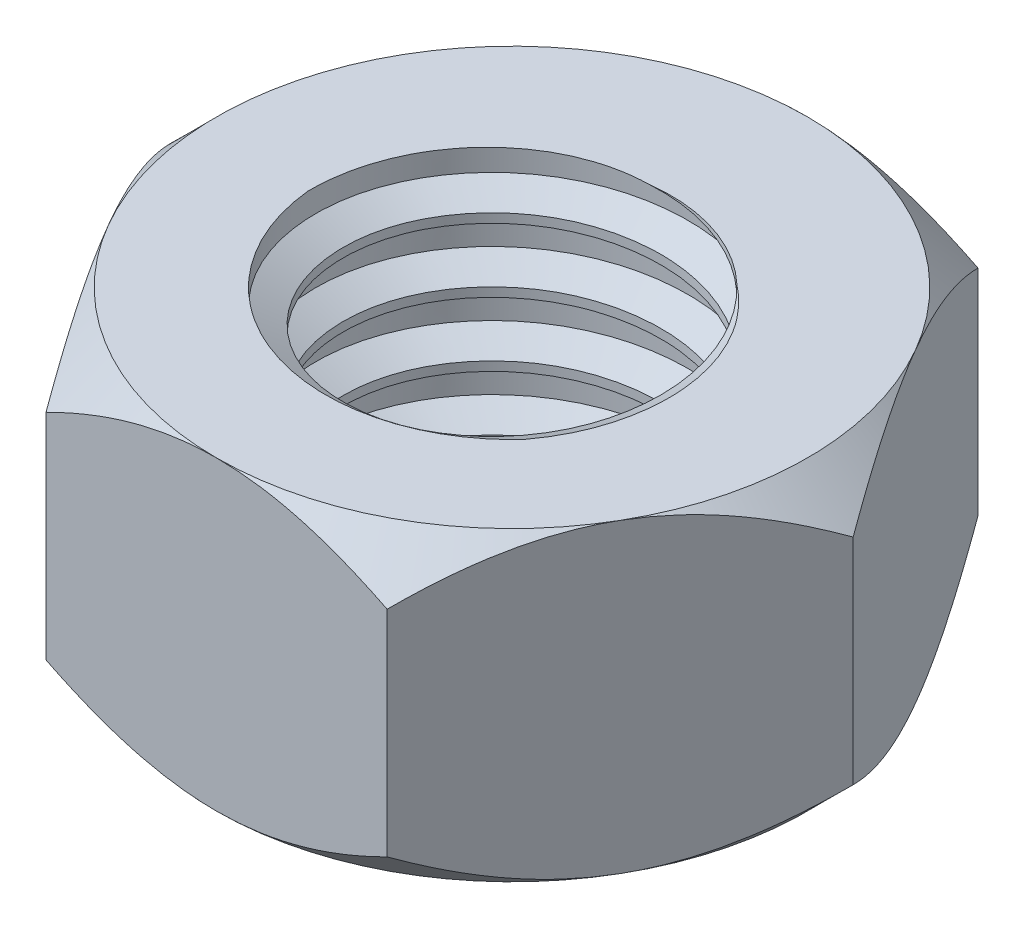
SolidWorks part; units mm, degrees
ref_plane "Front Plane" through (0, 0, 0) normal (0, 0, 1) x (1, 0, 0)
ref_plane "Top Plane" through (0, 0, 0) normal (0, 1, 0) x (1, 0, 0)
ref_plane "Right Plane" through (0, 0, 0) normal (1, 0, 0) x (0, 0, -1)
sketch "Sketch1" plane through (0, 0, 0) normal (0, 1, 0) x (1, 0, 0)
  line L1 (7.5056, 0) -> (3.7528, 6.5)
  line L2 (3.7528, 6.5) -> (-3.7528, 6.5)
  line L3 (-3.7528, 6.5) -> (-7.5056, 0)
  line L4 (-7.5056, 0) -> (-3.7528, -6.5)
  line L5 (-3.7528, -6.5) -> (3.7528, -6.5)
  line L6 (3.7528, -6.5) -> (7.5056, 0)
  circle A0 centre (0, 0) radius 3.5
  circle A1 centre (0, 0) radius 6.5 construction
  dimension "D1" = 13
  dimension "D2" = 7
extrude "Boss-Extrude1" add sketch "Sketch1" along normal blind 6.731
ref_axis "Axis1" through (0, 6.731, 0) along (0, -1, 0)
sketch "Sketch3" plane through (0, 0, 0) normal (0, -1, 0) x (1, 0, 0)
  circle A0 centre (0, 0) radius 3.5 construction
  circle A1 centre (0, 0) radius 3.5
curve "Helix/Spiral1" pitch 1.4111 height 13.429 radius 3.5 centre (0, 0, 0) axis (0, 1, 0) start towards (0, 0, -1)
sketch "Sketch2" plane through (0, 0, 0) normal (0, 0, 1) x (1, 0, 0)
  line L0 (-3.5, 0) -> (-4.1, -0.3464)
  line L1 (-4.1, -0.3464) -> (-4.1, -0.8647)
  line L2 (-4.1, -0.8647) -> (-3.5, -1.2111)
  line L3 (-3.5, 0) -> (-3.5, -1.2111)
  line L6 (-3.5, -1.2111) -> (-3.5, -1.4111) construction
  dimension "D1" = 4.1
  dimension "D2" = 1.4111
  dimension "D3" = 120
  dimension "D4" = 120
  dimension "D5" = 0.2
sweep "Cut-Sweep3" cut profiles "Sketch2" path "Helix/Spiral1"
sketch "Sketch4" plane through (0, 6.731, 0) normal (0, 1, 0) x (1, 0, 0)
  circle A0 centre (0, 0) radius 6.5
extrude "Cut-Extrude1" cut sketch "Sketch4" against normal blind 6.731 draft 45 flip side to cut
sketch "Sketch5" plane through (0, 0, 0) normal (0, -1, 0) x (1, 0, 0)
  circle A0 centre (0, 0) radius 6.5
extrude "Cut-Extrude2" cut sketch "Sketch5" against normal blind 6.731 draft 45 flip side to cut
